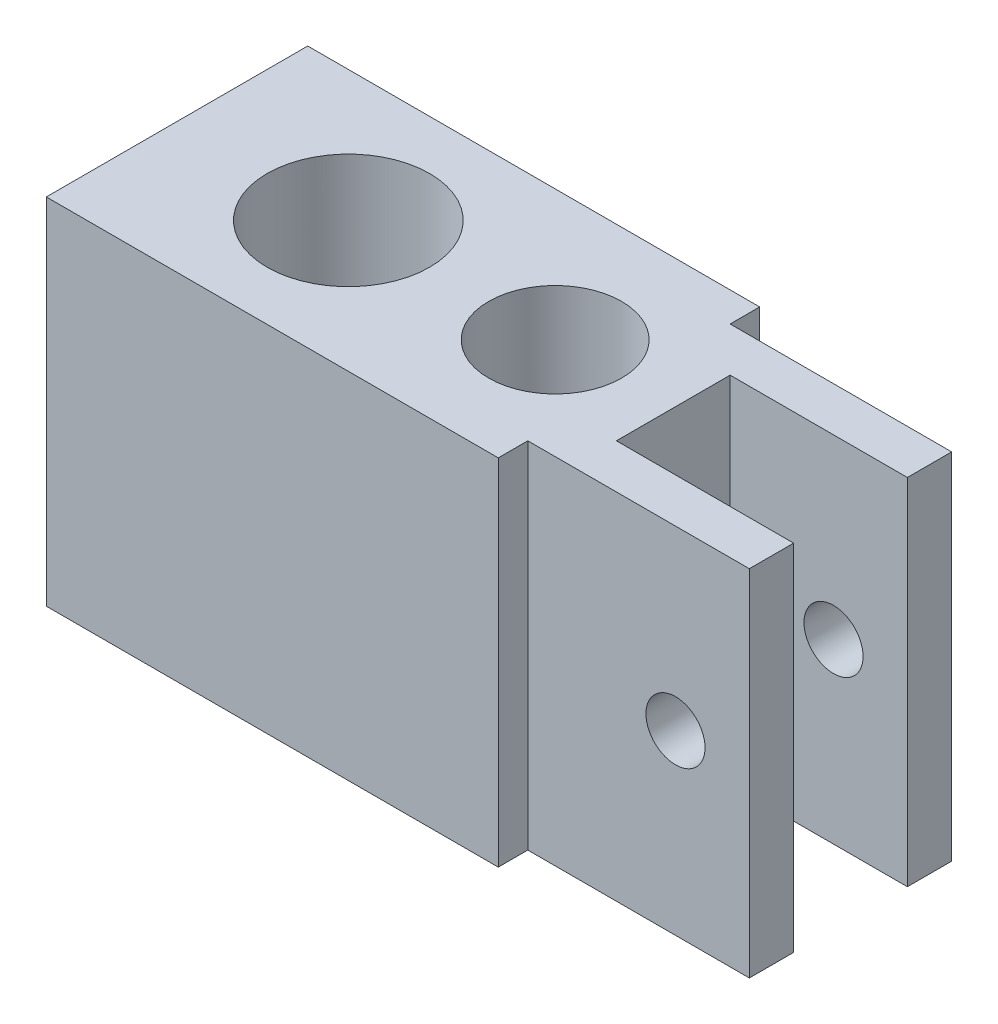
SolidWorks part; units mm, degrees
ref_plane "Ebene vorne" through (0, 0, 0) normal (0, 0, 1) x (1, 0, 0)
ref_plane "Ebene oben" through (0, 0, 0) normal (0, 1, 0) x (1, 0, 0)
ref_plane "Ebene rechts" through (0, 0, 0) normal (1, 0, 0) x (0, 0, -1)
sketch "Skizze1" plane through (0, 0, 0) normal (0, 0, 1) x (1, 0, 0)
  line L1 (-11.6, 468.1) -> (34, 468.1)
  line L2 (-11.6, 468.1) -> (-11.6, 444.1)
  line L3 (-11.6, 444.1) -> (34, 444.1)
  line L4 (34, 468.1) -> (34, 444.1)
  circle A0 centre (29, 456.1) radius 2
  point P6 (-11.6, 456.1)
sketch "Skizze2" plane through (0, 0, 0) normal (0, 1, 0) x (1, 0, 0)
  line L1 (-12.6, 8.85) -> (19, 8.85)
  line L2 (-12.6, 8.85) -> (-12.6, -8.85)
  line L3 (-12.6, 0) -> (22, 0)
  line L4 (34, 6.85) -> (34, 3.85)
  line L8 (34, 6.85) -> (19, 6.85)
  line L9 (19, 8.85) -> (19, 6.85)
  line L10 (19, -8.85) -> (19, -6.85)
  line L11 (34, -6.85) -> (19, -6.85)
  line L12 (-12.6, -8.85) -> (19, -8.85)
  line L13 (34, -3.85) -> (22, -3.85)
  line L14 (34, 3.85) -> (22, 3.85)
  line L17 (22, 3.85) -> (22, -3.85)
  line L18 (34, -3.85) -> (34, -6.85)
  circle A0 centre (14, 0) radius 4.5
  circle A1 centre (0, 0) radius 5.5
sketch "Skizze3" plane through (0, 0, 0) normal (0, 1, 0) x (1, 0, 0)
  line L0 (-12.6, -8.85) -> (-12.6, 8.85)
  line L1 (-12.6, 8.85) -> (19, 8.85)
  line L2 (19, 8.85) -> (19, 6.85)
  line L3 (19, 6.85) -> (34, 6.85)
  line L5 (-65.0925, 0) -> (65.0925, 0) construction
  line L6 (19, -6.85) -> (34, -6.85)
  line L7 (19, -8.85) -> (19, -6.85)
  line L8 (-12.6, -8.85) -> (19, -8.85)
  line L9 (34, 6.85) -> (34, 3.85)
  line L10 (22, -3.85) -> (22, 3.85)
  line L11 (22, 3.85) -> (34, 3.85)
  line L12 (-25.63, 0) -> (25.63, 0) construction
  line L13 (34, -6.85) -> (34, -3.85)
  line L14 (22, -3.85) -> (34, -3.85)
  circle A0 centre (0, 0) radius 5.5
  circle A1 centre (14, 0) radius 4.5
  point P21 (34, 0)
  point P24 (-12.6, 0)
  point P34 (22, 0)
sketch "Skizze5" plane through (0, 0, 0) normal (0, 0, 1) x (1, 0, 0)
  line L1 (-11.6, 468.1) -> (34, 468.1)
  line L2 (-11.6, 468.1) -> (-11.6, 444.1)
  line L3 (-11.6, 444.1) -> (34, 444.1)
  line L4 (34, 468.1) -> (34, 444.1)
  circle A0 centre (29, 456.1) radius 2
extrude "Aufsatz-Linear austragen1" add sketch "Skizze3" along normal up to vertex (468.1 mm away) up to point (34, 468.1, 0)
extrude "Schnitt-Linear austragen2" cut sketch "Skizze5" against normal through all both and the other way through all flip side to cut
